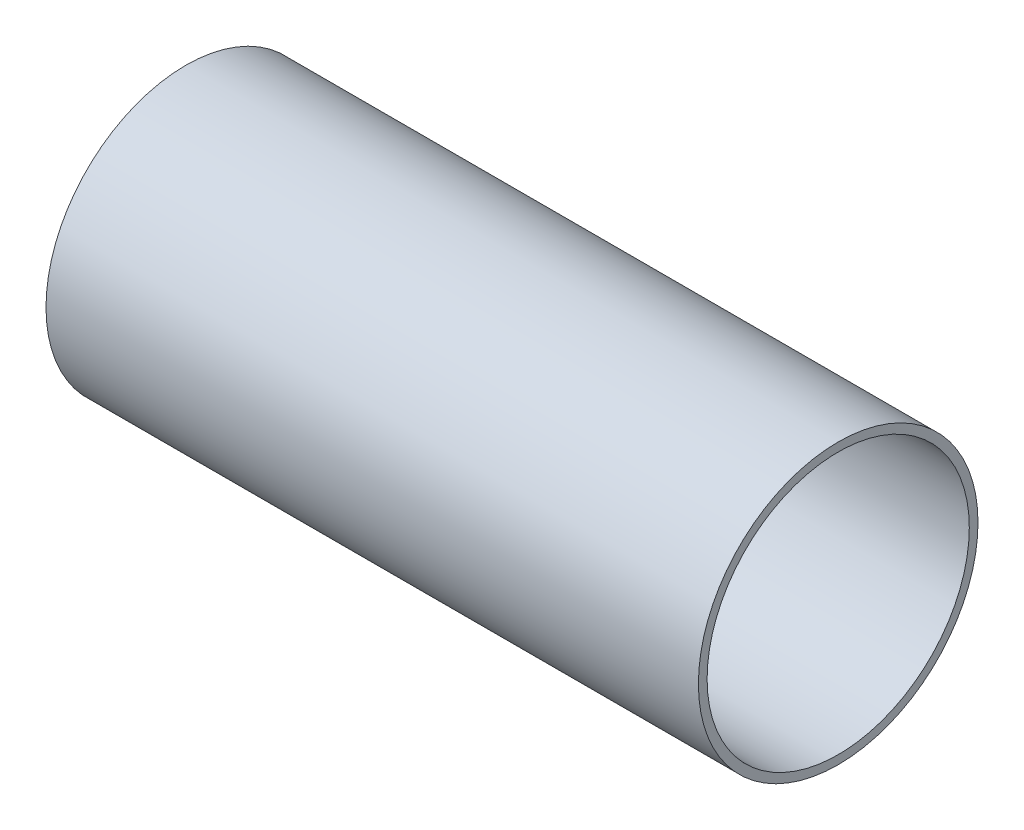
SolidWorks part; units mm, degrees
ref_plane "Front Plane" through (0, 0, 0) normal (0, 0, 1) x (1, 0, 0)
ref_plane "Top Plane" through (0, 0, 0) normal (0, 1, 0) x (1, 0, 0)
ref_plane "Right Plane" through (0, 0, 0) normal (1, 0, 0) x (0, 0, -1)
sketch "Sketch1" plane through (0, 0, 0) normal (1, 0, 0) x (0, 0, -1)
  circle A0 centre (0, 0) radius 14.2875
  circle A1 centre (0, 0) radius 13.3985
extrude "Boss-Extrude1" add sketch "Sketch1" along normal mid plane 66.675
